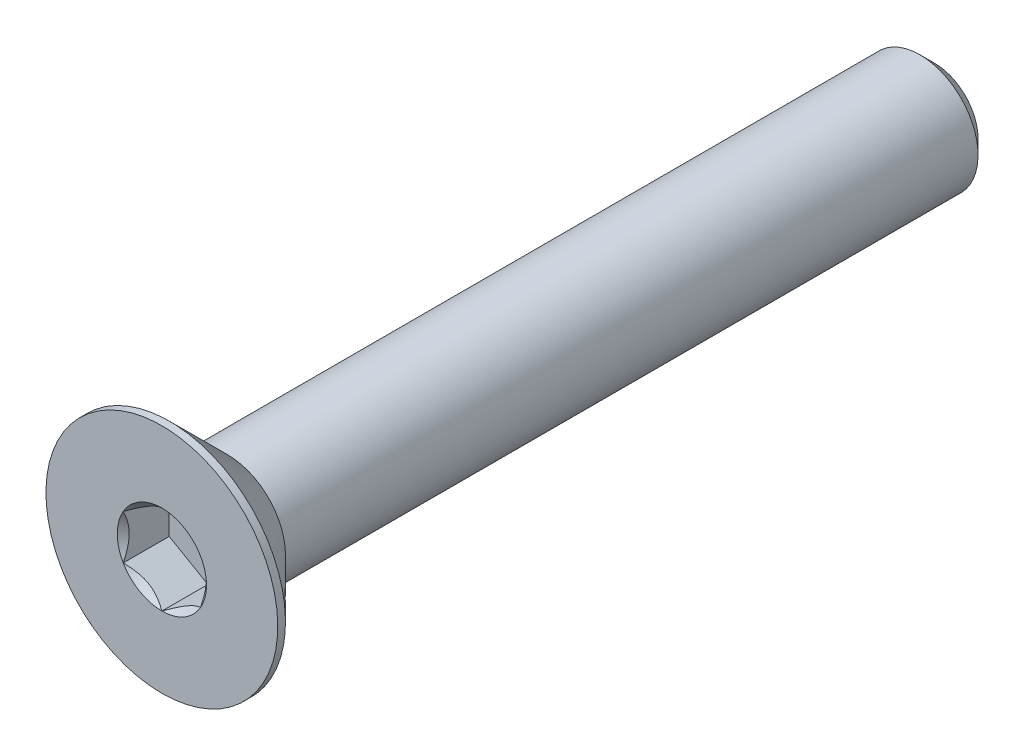
SolidWorks part; units mm, degrees
ref_plane "Front" through (0, 0, 0) normal (0, 0, 1) x (1, 0, 0)
ref_plane "Top" through (0, 0, 0) normal (0, 1, 0) x (1, 0, 0)
ref_plane "Right" through (0, 0, 0) normal (1, 0, 0) x (0, 0, -1)
sketch "Sketch1" plane through (0, 0, 0) normal (1, 0, 0) x (0, 0, -1)
  line L0 (0, 3) -> (0.2, 3) construction
  line L1 (0.2, 3) -> (1.7, 1.5) construction
  line L2 (0, 1.5) -> (20, 1.5)
  line L3 (20, 1.5) -> (20, 0)
  line L4 (20, 0) -> (0, 0)
  line L5 (0, 0) -> (0, 3) construction
  line L6 (0, 3) -> (0, -3) construction
  line L7 (20, 1.5) -> (20, -1.5) construction
  line L8 (0, -3) -> (0.2, -3) construction
  line L9 (0.2, -3) -> (1.7, -1.5) construction
  line L11 (0, 1.5) -> (0, 0)
  line L12 (1.7, 1.5) -> (1.7, 0) construction
revolve "Revolve1" add sketch "Sketch1" angle 360 mid plane about L4
sketch "Sketch3" plane through (0, 0, -20) normal (0, 0, -1) x (-1, 0, 0)
  circle A0 centre (0, 0) radius 1.5
curve "Helix/Spiral1" pitch 0.5 height 20 turns 40
sketch "Sketch2" plane through (0, 0, 0) normal (1, 0, 0) x (0, 0, -1)
  line L0 (20, 1.5) -> (20.4375, 1.5)
  line L1 (20.4375, 1.5) -> (20.25, 1.1752)
  line L2 (20.25, 1.1752) -> (20.1875, 1.1752)
  line L3 (20.1875, 1.1752) -> (20, 1.5)
  line L4 (20.0938, 1.3376) -> (20.3438, 1.3376) construction
  dimension "D1" = 60
  dimension "D2" = 0.0625
  dimension "D3" = 0.25
chamfer "Chamfer1" distance 0.375 angle 45 1 edges at (0, 1.5, -20)
sweep "Cut-Sweep1" [suppressed] cut profiles "Sketch2" path "Helix/Spiral1"
sketch "Sketch7" plane through (0, 0, 0) normal (1, 0, 0) x (0, 0, -1)
  line L0 (0, 3) -> (0.2, 3) construction
  line L1 (0.2, 3) -> (1.7, 1.5) construction
  line L2 (0, 3) -> (0.2, 3)
  line L3 (0.2, 3) -> (1.7, 1.5)
  line L4 (1.7, 1.5) -> (1.7, 0) construction
  line L5 (1.7, 1.5) -> (1.7, 0)
  line L7 (0, 0) -> (0, 3) construction
  line L8 (0, 0) -> (0, 3)
  line L9 (0, 0) -> (1.7, 0)
  line L10 (3.3, 0) -> (-3.3, 0) construction
revolve "Revolve2" add sketch "Sketch7" angle 360 mid plane about L9
ref_plane "Plane1" through (0, 0, -1.7) normal (0, 0, 1) x (1, 0, 0)
sketch "Sketch8" plane through (0, 0, -1.7) normal (0, 0, 1) x (1, 0, 0)
  circle A0 centre (0, 0) radius 1.5
extrude "Boss-Extrude1" add sketch "Sketch8" against normal through all draft 45
sketch "Sketch5" plane through (0, 0, 0) normal (0, 0, 1) x (1, 0, 0)
  line L1 (1, -0.5774) -> (1, 0.5774)
  line L2 (1, 0.5774) -> (0, 1.1547)
  line L3 (0, 1.1547) -> (-1, 0.5774)
  line L4 (-1, 0.5774) -> (-1, -0.5774)
  line L5 (-1, -0.5774) -> (0, -1.1547)
  line L6 (0, -1.1547) -> (1, -0.5774)
  circle A0 centre (0, 0) radius 1 construction
  dimension "Hex" = 2
extrude "Cut-Extrude2" cut sketch "Sketch5" against normal blind 1.19
sketch "Sketch6" plane through (0, 0, 0) normal (0, 0, 1) x (1, 0, 0)
  circle A0 centre (0, 0) radius 1.1547
extrude "Cut-Extrude3" cut sketch "Sketch6" against normal blind 1.19 draft 45
sketch "Sketch9" [suppressed] plane through (0, 0, -4.4) normal (0, 0, 1) x (1, 0, 0)
  circle A1 centre (0, 0) radius 4
  circle A2 centre (0, 0) radius 4
  point P0 (0, 4)
  dimension "D1" = 0
extrude "Boss-Extrude2" [suppressed] add sketch "Sketch9" against normal offset from surface (0.6 mm away) 26
fillet "Fillet1" [suppressed] radius 0.3
sketch "Sketch10" plane through (0, 0, 0) normal (1, 0, 0) x (0, 0, -1)
  line L0 (20, 1.5) -> (20, -1.5) construction
  point P0 (19.25, -1.5)
  dimension "D1" = 0.75
equation "\"D3@Helix/Spiral1\" = \"Lg@Sketch1\""
equation "\"D2@Sketch2\" = \"D4@Helix/Spiral1\" * .125"
equation "\"D3@Sketch2\" = \"D4@Helix/Spiral1\" * .5"
equation "\"D1@Chamfer1\" = \"D4@Helix/Spiral1\" * .75"
equation "\"D1@Cut-Extrude2\" = \"Head Ht@Sketch1\" * .7"
equation "\"D1@Sketch10\" = \"D4@Helix/Spiral1\" * 1.5"
equation "\"D1@Cut-Extrude3\" = \"D1@Cut-Extrude2\""
equation "\"D1@Fillet1\" = \"Dia@Sketch1\" * .1"
